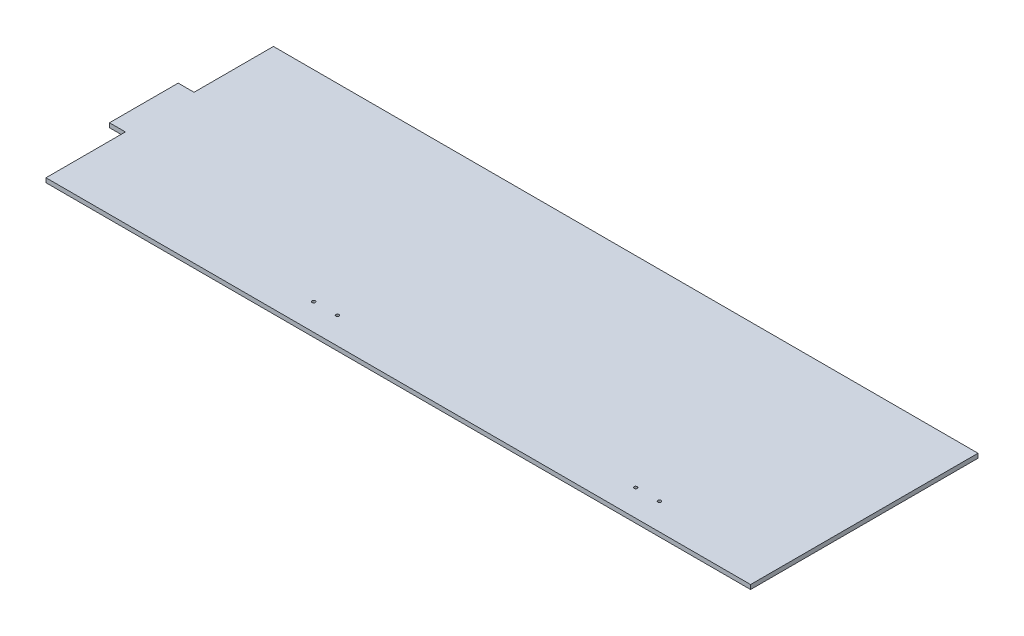
SolidWorks part; units mm, degrees
ref_plane "Front Plane" through (0, 0, 0) normal (0, 0, 1) x (1, 0, 0)
ref_plane "Top Plane" through (0, 0, 0) normal (0, 1, 0) x (1, 0, 0)
ref_plane "Right Plane" through (0, 0, 0) normal (1, 0, 0) x (0, 0, -1)
sketch "Sketch1" plane through (0, 0, 0) normal (0, 1, 0) x (1, 0, 0)
  line L0 (-280, 21.6257) -> (-270, 21.6257)
  line L1 (-270, 71.6257) -> (270, 71.6257)
  line L2 (-270, 71.6257) -> (-270, 21.6257)
  line L3 (-270, -71.6257) -> (270, -71.6257)
  line L4 (270, 71.6257) -> (270, -71.6257)
  line L5 (-270, 71.6257) -> (270, -71.6257) construction
  line L6 (-270, -71.6257) -> (270, 71.6257) construction
  line L7 (-280, 21.6257) -> (-280, -21.6257)
  line L8 (-280, -21.6257) -> (-270, -21.6257)
  line L9 (-270, -21.6257) -> (-270, -71.6257)
  line L10 (-270, 22.6702) -> (-270, 21.6257) construction
  line L11 (173.8, 71.6257) -> (173.8, -71.6257)
  line L13 (178.8, 62.23) -> (178.8, -62.23) construction
  circle A5 centre (99.6713, -54.904) radius 1 construction
  circle A6 centre (84.6713, -54.904) radius 1 construction
  circle A7 centre (-103.1287, -54.904) radius 1 construction
  circle A8 centre (-118.1287, -54.904) radius 1 construction
  circle A9 centre (99.6713, -54.904) radius 1
  circle A10 centre (84.6713, -54.904) radius 1
  circle A11 centre (-103.1287, -54.904) radius 1
  circle A12 centre (-118.1287, -54.904) radius 1
  point P4 (0, 0)
  dimension "D1" = 50
  dimension "D2" = 50
  dimension "D3" = 5
  dimension "D6" = 10
  dimension "D7" = 540
  dimension "D8" = 143.2513
extrude "Boss-Extrude1" add sketch "Sketch1" along normal blind 2.7432 from offset 2 contours L8 L9 L3 L4 L1 L2 L0 L7 region at (-49.6412, 0, -0.0108)
